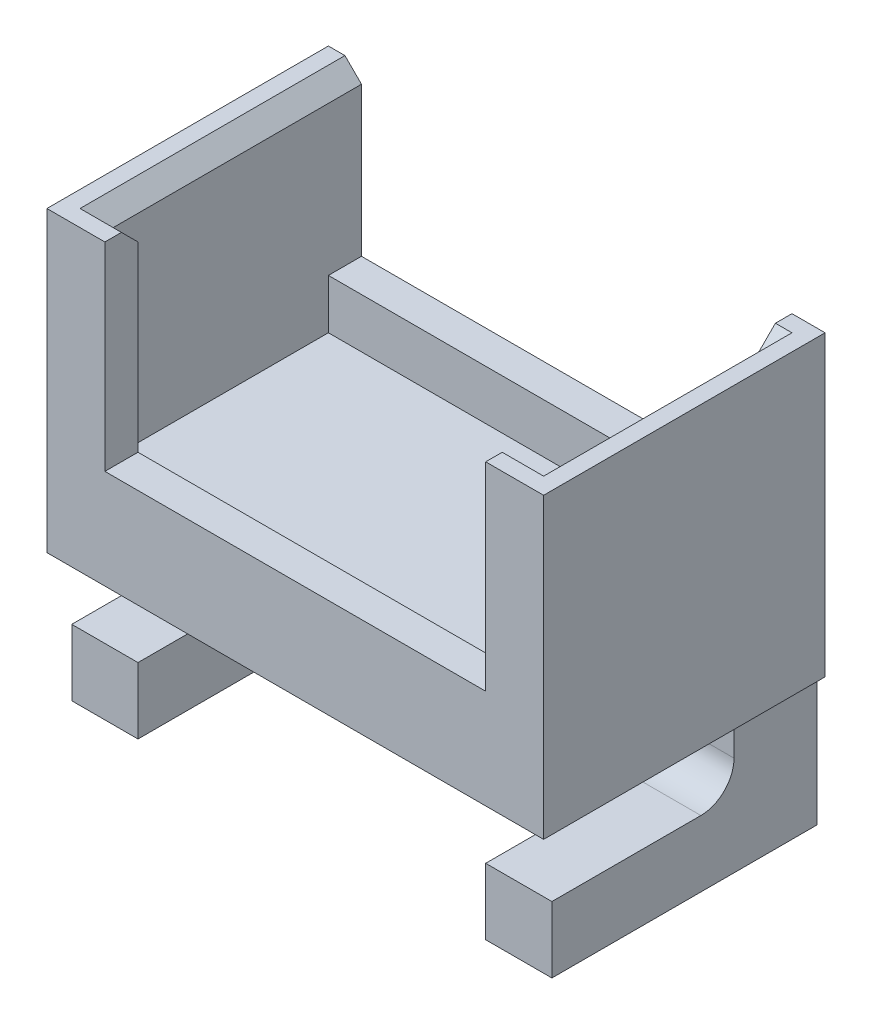
SolidWorks part; units mm, degrees
ref_plane "前视基准面" through (0, 0, 0) normal (0, 0, 1) x (1, 0, 0)
ref_plane "上视基准面" through (0, 0, 0) normal (0, 1, 0) x (1, 0, 0)
ref_plane "右视基准面" through (0, 0, 0) normal (1, 0, 0) x (0, 0, -1)
sketch "草图2" plane through (0, 0, 0) normal (0, 1, 0) x (1, 0, 0)
  line L1 (-13, 6.5) -> (13, 6.5)
  line L2 (-13, 6.5) -> (-13, -6.5)
  line L3 (-13, -6.5) -> (13, -6.5)
  line L4 (13, 6.5) -> (13, -6.5)
  line L5 (15, 8.5) -> (-15, 8.5)
  line L6 (15, 8.5) -> (15, -8.5)
  line L7 (15, -8.5) -> (-15, -8.5)
  line L8 (-15, 8.5) -> (-15, -8.5)
  line L9 (15, 8.5) -> (-15, -8.5) construction
  line L10 (15, -8.5) -> (-15, 8.5) construction
  point P0 (0, 0)
  point P6 (0, 0)
  dimension "D1" = 26
  dimension "D2" = 13
  dimension "D3" = 2
  dimension "D4" = 2
  dimension "D5" = 2
  dimension "D6" = 2
extrude "凸台-拉伸1" add sketch "草图2" along normal blind 2 contours L8 L7 L6 L5
extrude "凸台-拉伸2" add sketch "草图2<3>" along normal blind 15
sketch "草图2<3>" plane through (0, 0, 0) normal (0, 1, 0) x (1, 0, 0) same geometry as "草图2"
sketch "草图3" plane through (0, 0, 8.5) normal (0, 0, 1) x (1, 0, 0)
  line L0 (-15, 15) -> (15, 15) construction
  line L1 (-11.5, 15) -> (11.5, 15)
  line L2 (-11.5, 15) -> (-11.5, 3)
  line L3 (-11.5, 3) -> (11.5, 3)
  line L4 (11.5, 15) -> (11.5, 3)
  line L5 (-15, 15) -> (-15, 0) construction
  line L6 (15, 15) -> (15, 0) construction
  line L7 (15, 0) -> (-15, 0) construction
  dimension "D1" = 3.5
  dimension "D2" = 3.5
  dimension "D3" = 3
extrude "切除-拉伸1" cut sketch "草图3" against normal up to next
sketch "草图4" plane through (0, 0, -6.5) normal (0, 0, 1) x (1, 0, 0)
  line L1 (-13, 15) -> (-1, 15)
  line L2 (-13, 15) -> (-13, 9)
  line L3 (-13, 9) -> (-1, 9)
  line L4 (-1, 15) -> (-1, 9)
  dimension "D1" = 6
  dimension "D2" = 12
extrude "切除-拉伸2" cut sketch "草图4" against normal up to next
chamfer "倒角2" distance 1 angle 45 5 edges at (-13, 15, -1) (-12.25, 15, 6.5) (12.25, 15, 6.5) (6, 15, -6.5) (13, 15, 0)
sketch "草图5" plane through (0, 0, 0) normal (0, -1, 0) x (1, 0, 0)
  line L4 (-15, -8.5) -> (15, -8.5)
  line L5 (15, -8.5) -> (15, 8.5)
  line L6 (15, 8.5) -> (-15, 8.5)
  line L7 (-15, 8.5) -> (-15, -8.5)
  line L8 (-15, -8.5) -> (15, -8.5)
  line L9 (15, -8.5) -> (15, 8.5)
  line L10 (15, 8.5) -> (-15, 8.5)
  line L11 (-15, 8.5) -> (-15, -8.5)
  dimension "D1" = 0
extrude "凸台-拉伸3" add sketch "草图5" along normal blind 3
sketch "草图6" plane through (0, -3, 0) normal (0, -1, 0) x (1, 0, 0)
  line L0 (0, 10.0552) -> (0, -10.982) construction
  line L1 (-12.5, 9.6026) -> (-12.5, -10.5941) construction
  line L2 (12.5, 9.6026) -> (12.5, -10.5941) construction
  line L3 (-12.5, -3.5) -> (-10.5, -3.5)
  line L5 (-12.5, -3.5) -> (-14.5, -3.5)
  line L6 (-15, -8.5) -> (15, -8.5) construction
  line L7 (-14.5, -3.5) -> (-14.5, -8.5)
  line L8 (-14.5, -8.5) -> (-10.5, -8.5)
  line L9 (-10.5, -8.5) -> (-10.5, -3.5)
  dimension "D1" = 12.5
  dimension "D2" = 2
  dimension "D3" = 2
  dimension "D4" = 5
extrude "凸台-拉伸4" add sketch "草图6" along normal blind 4
sketch "草图7" plane through (0, 0, -8.5) normal (0, 0, -1) x (-1, 0, 0)
  line L0 (14.5, -7) -> (14.5, -11)
  line L1 (14.5, -11) -> (10.5, -11)
  line L2 (10.5, -11) -> (10.5, -7)
  line L3 (10.5, -7) -> (14.5, -7)
  dimension "D1" = 4
extrude "凸台-拉伸5" add sketch "草图7" against normal blind 16
mirror "镜向1" about plane through (0, 0, 0) normal (1, 0, 0) of "凸台-拉伸5", "凸台-拉伸4"
fillet "圆角1" radius 2 2 edges at (12.5, -7, -3.5) (-12.5, -7, -3.5)
sketch "草图8" plane through (0, 15, 0) normal (0, 1, 0) x (1, 0, 0)
  line L0 (13, 6.5) -> (13, 9.5175)
  line L1 (13, 9.5175) -> (-13, 9.5175)
  line L2 (-13, 9.5175) -> (-13, 5.7999)
  line L3 (-13, 5.7999) -> (12.8356, 5.7999)
  line L4 (12.8356, 5.7999) -> (13, 6.5)
  line L5 (-13, -6.5) -> (-13, 6.5) construction
extrude "切除-拉伸3" cut sketch "草图8" against normal blind 10
